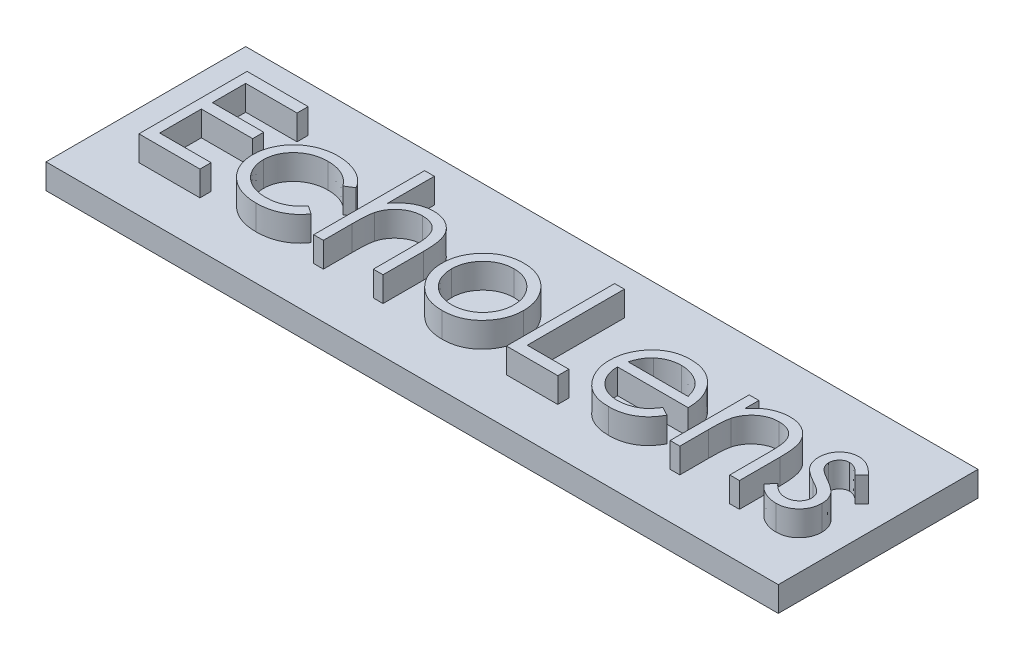
SolidWorks part; units mm, degrees
ref_plane "Front Plane" through (0, 0, 0) normal (0, 0, 1) x (1, 0, 0)
ref_plane "Top Plane" through (0, 0, 0) normal (0, 1, 0) x (1, 0, 0)
ref_plane "Right Plane" through (0, 0, 0) normal (1, 0, 0) x (0, 0, -1)
sketch "Sketch1" plane through (0, 0, 0) normal (0, 1, 0) x (1, 0, 0)
  line L0 (-20, 0) -> (20, 0) construction
  line L1 (-19.1667, 6.5) -> (-15.5, 6.5)
  line L2 (-15.5, 6.5) -> (-15.5, 5.8333)
  line L3 (-15.5, 5.8333) -> (-18.5833, 5.8333)
  line L4 (-18.5833, 5.8333) -> (-18.5833, 3.8333)
  line L5 (-18.5833, 3.8333) -> (-15.5, 3.8333)
  line L6 (-15.5, 3.8333) -> (-15.5, 3.1667)
  line L7 (-15.5, 3.1667) -> (-18.5833, 3.1667)
  line L8 (-18.5833, 3.1667) -> (-18.5833, 0.6667)
  line L9 (-18.5833, 0.6667) -> (-15.5, 0.6667)
  line L10 (-15.5, 0.6667) -> (-15.5, 0)
  line L11 (-15.5, 0) -> (-19.1667, 0)
  line L12 (-19.1667, 0) -> (-19.1667, 6.5)
  line L13 (-9.8333, 3.7201) -> (-10.3216, 3.4167)
  line L14 (-10.3216, 1.3333) -> (-9.8333, 1.013)
  line L15 (-8.6667, 6.6667) -> (-8.0833, 6.6667)
  line L16 (-8.0833, 6.6667) -> (-8.0833, 3.8529)
  line L17 (-4.5, 2.4258) -> (-4.5, 0)
  line L18 (-4.5, 0) -> (-5.0833, 0)
  line L19 (-5.0833, 0) -> (-5.0833, 2.2344)
  line L20 (-8.0833, 1.7174) -> (-8.0833, 0)
  line L21 (-8.0833, 0) -> (-8.6667, 0)
  line L22 (-8.6667, 0) -> (-8.6667, 6.6667)
  line L23 (2.9167, 6.5) -> (3.5, 6.5)
  line L24 (3.5, 6.5) -> (3.5, 0.6667)
  line L25 (3.5, 0.6667) -> (6, 0.6667)
  line L26 (6, 0.6667) -> (6, 0)
  line L27 (6, 0) -> (2.9167, 0)
  line L28 (2.9167, 0) -> (2.9167, 6.5)
  line L29 (10.8151, 1.5) -> (11.3333, 1.2279)
  line L30 (11.5833, 2.25) -> (7.3333, 2.25)
  line L31 (7.3945, 2.8333) -> (11, 2.8333)
  line L32 (12.75, 4.75) -> (13.3333, 4.75)
  line L33 (13.3333, 4.75) -> (13.3333, 3.8932)
  line L34 (16.9167, 2.4258) -> (16.9167, 0)
  line L35 (16.9167, 0) -> (16.3333, 0)
  line L36 (16.3333, 0) -> (16.3333, 2.2344)
  line L37 (13.3333, 1.7174) -> (13.3333, 0)
  line L38 (13.3333, 0) -> (12.75, 0)
  line L39 (12.75, 0) -> (12.75, 4.75)
  line L40 (20.5, 4.1576) -> (20.1042, 3.75)
  line L41 (17.8333, 0.5599) -> (18.2201, 1)
  line L43 (-22, 9.25) -> (22, 9.25)
  line L44 (-22, 9.25) -> (-22, -2.75)
  line L45 (-22, -2.75) -> (22, -2.75)
  line L46 (22, 9.25) -> (22, -2.75)
  spline S0 degree 3 poles (-10.3216, 3.4167) (-10.4224, 3.5511) (-10.5946, 3.7325) (-10.8586, 3.9283) (-11.0689, 4.0467) (-11.2944, 4.138) (-11.6201, 4.2264) (-11.877, 4.2503) (-12.0508, 4.25) knots 0 0 0 0 0.252584 0.373506 0.493364 0.614609 0.73847 1 1 1 1
  spline S1 degree 3 poles (-12.0508, 4.25) (-12.1908, 4.248) (-12.3987, 4.2357) (-12.6645, 4.1761) (-12.8521, 4.1183) (-13.0299, 4.0407) (-13.1982, 3.9464) (-13.3587, 3.8367) (-13.5065, 3.7096) (-13.6418, 3.5715) (-13.759, 3.4234) (-13.861, 3.2697) (-13.9411, 3.1068) (-14.0065, 2.9382) (-14.065, 2.699) (-14.084, 2.5135) (-14.0833, 2.388) knots 0 0 0 0 0.136921 0.201969 0.265462 0.328248 0.390817 0.45355 0.517542 0.580738 0.641922 0.701597 0.760313 0.818757 0.877718 1 1 1 1
  spline S2 degree 3 poles (-14.0833, 2.388) (-14.0829, 2.223) (-14.0506, 1.9744) (-13.9377, 1.6602) (-13.8226, 1.4342) (-13.6768, 1.2251) (-13.5056, 1.0376) (-13.3089, 0.8753) (-13.0884, 0.7406) (-12.8493, 0.6325) (-12.504, 0.5277) (-12.2309, 0.5007) (-12.0469, 0.5) knots 0 0 0 0 0.159965 0.240321 0.322529 0.405024 0.486597 0.567865 0.651333 0.736238 0.821529 1 1 1 1
  spline S3 degree 3 poles (-12.0469, 0.5) (-11.8779, 0.5001) (-11.6274, 0.5237) (-11.3088, 0.6127) (-11.0852, 0.7038) (-10.874, 0.8219) (-10.6058, 1.0188) (-10.4279, 1.1994) (-10.3216, 1.3333) knots 0 0 0 0 0.255447 0.377298 0.498442 0.619372 0.741857 1 1 1 1
  spline S4 degree 3 poles (-9.8333, 1.013) (-9.8897, 0.9272) (-9.9815, 0.8035) (-10.121, 0.6539) (-10.2323, 0.5497) (-10.3495, 0.4508) (-10.4764, 0.3619) (-10.6089, 0.2781) (-10.7487, 0.2027) (-10.8942, 0.1349) (-11.0453, 0.0766) (-11.2012, 0.0265) (-11.3623, -0.0133) (-11.5287, -0.0451) (-11.76, -0.0738) (-11.9367, -0.0852) (-12.056, -0.0833) knots 0 0 0 0 0.119069 0.178197 0.236957 0.295932 0.355856 0.416473 0.477742 0.539903 0.602538 0.665422 0.729765 0.794829 0.861827 1 1 1 1
  spline S5 degree 3 poles (-12.056, -0.0833) (-12.2366, -0.0852) (-12.5029, -0.0624) (-12.8456, 0.0111) (-13.0864, 0.0882) (-13.3154, 0.1876) (-13.5325, 0.3089) (-13.7368, 0.4533) (-13.9265, 0.6182) (-14.1006, 0.7969) (-14.2502, 0.9898) (-14.3799, 1.1897) (-14.4841, 1.4011) (-14.5669, 1.6211) (-14.6438, 1.9318) (-14.6672, 2.173) (-14.6667, 2.3359) knots 0 0 0 0 0.136335 0.201096 0.26445 0.327005 0.389391 0.451976 0.51567 0.578973 0.640167 0.69974 0.758685 0.81782 0.876984 1 1 1 1
  spline S6 degree 3 poles (-14.6667, 2.3359) (-14.6683, 2.4476) (-14.654, 2.6135) (-14.6213, 2.8322) (-14.5805, 2.9912) (-14.5332, 3.1483) (-14.4729, 3.3017) (-14.4022, 3.452) (-14.3219, 3.5989) (-14.2314, 3.7399) (-14.1314, 3.8732) (-14.0254, 4.0003) (-13.9087, 4.1167) (-13.786, 4.2273) (-13.654, 4.329) (-13.5134, 4.4221) (-13.3664, 4.5084) (-13.2129, 4.5852) (-13.054, 4.6514) (-12.8906, 4.7079) (-12.7224, 4.7527) (-12.5506, 4.7902) (-12.3122, 4.8223) (-12.1306, 4.834) (-12.0078, 4.8333) knots 0 0 0 0 0.082136 0.122636 0.162831 0.203007 0.243526 0.284173 0.32541 0.366855 0.407551 0.448187 0.488683 0.529015 0.569843 0.61137 0.653238 0.695446 0.737751 0.780043 0.822807 0.865978 0.909595 1 1 1 1
  spline S7 degree 3 poles (-12.0078, 4.8333) (-11.8526, 4.8338) (-11.6211, 4.8144) (-11.3179, 4.7561) (-11.0985, 4.6919) (-10.8891, 4.6142) (-10.6931, 4.5269) (-10.5151, 4.4255) (-10.3518, 4.3146) (-10.203, 4.1894) (-10.019, 3.9996) (-9.9014, 3.8368) (-9.8333, 3.7201) knots 0 0 0 0 0.182081 0.27191 0.362049 0.450066 0.533976 0.613602 0.690198 0.765413 0.841437 1 1 1 1
  spline S8 degree 3 poles (-8.0833, 3.8529) (-7.966, 4.0089) (-7.7716, 4.2191) (-7.4828, 4.4546) (-7.2593, 4.5919) (-7.0271, 4.7002) (-6.7025, 4.8039) (-6.4468, 4.833) (-6.276, 4.8333) knots 0 0 0 0 0.273996 0.400684 0.522555 0.641534 0.759969 1 1 1 1
  spline S9 degree 3 poles (-6.276, 4.8333) (-6.1045, 4.8322) (-5.8484, 4.8043) (-5.5317, 4.6878) (-5.315, 4.5706) (-5.1203, 4.4244) (-4.9479, 4.2558) (-4.8071, 4.0602) (-4.7112, 3.8796) (-4.6489, 3.7189) (-4.6094, 3.581) (-4.576, 3.4274) (-4.5468, 3.2581) (-4.5274, 3.0723) (-4.5056, 2.7934) (-4.4986, 2.5761) (-4.5, 2.4258) knots 0 0 0 0 0.151155 0.223454 0.295497 0.36692 0.436794 0.506696 0.577864 0.615912 0.658048 0.703776 0.75408 0.808979 0.867913 1 1 1 1
  spline S10 degree 3 poles (-5.0833, 2.2344) (-5.0842, 2.3581) (-5.0846, 2.5352) (-5.0916, 2.7605) (-5.0996, 2.9041) (-5.1082, 3.031) (-5.1224, 3.1665) (-5.1379, 3.2593) (-5.151, 3.3151) knots 0 0 0 0 0.342141 0.489871 0.623312 0.740056 0.841468 1 1 1 1
  spline S11 degree 3 poles (-5.151, 3.3151) (-5.1871, 3.4575) (-5.2624, 3.6607) (-5.4263, 3.8872) (-5.5708, 4.0208) (-5.739, 4.1255) (-6.0064, 4.2265) (-6.2273, 4.2507) (-6.3789, 4.25) knots 0 0 0 0 0.261954 0.379638 0.494379 0.609866 0.729887 1 1 1 1
  spline S12 degree 3 poles (-6.3789, 4.25) (-6.4717, 4.2504) (-6.6105, 4.2399) (-6.79, 4.2011) (-6.9207, 4.1623) (-7.0459, 4.1095) (-7.1691, 4.0483) (-7.2868, 3.9735) (-7.4012, 3.8895) (-7.5076, 3.7965) (-7.6066, 3.6983) (-7.6949, 3.5938) (-7.7749, 3.4846) (-7.8439, 3.3692) (-7.9247, 3.2082) (-7.9701, 3.08) (-7.9935, 2.9922) knots 0 0 0 0 0.126694 0.189084 0.250363 0.312516 0.374243 0.43785 0.502657 0.567745 0.630576 0.692772 0.754268 0.815121 0.876051 1 1 1 1
  spline S13 degree 3 poles (-7.9935, 2.9922) (-8.0109, 2.9236) (-8.0304, 2.8103) (-8.0495, 2.6461) (-8.0626, 2.4958) (-8.0707, 2.3269) (-8.0827, 2.0657) (-8.0825, 1.8602) (-8.0833, 1.7174) knots 0 0 0 0 0.165611 0.269045 0.387448 0.518827 0.665394 1 1 1 1
  spline S14 degree 3 poles (-0.8724, 4.8333) (-0.6977, 4.8351) (-0.4391, 4.8099) (-0.1083, 4.727) (0.1253, 4.6431) (0.3452, 4.5303) (0.6281, 4.3491) (0.8169, 4.1769) (0.9323, 4.0508) knots 0 0 0 0 0.258332 0.382134 0.503804 0.624693 0.746871 1 1 1 1
  spline S15 degree 3 poles (0.9323, 4.0508) (1.0382, 3.935) (1.1801, 3.7494) (1.3328, 3.4813) (1.424, 3.2729) (1.4958, 3.0568) (1.5648, 2.7542) (1.5825, 2.5197) (1.5833, 2.362) knots 0 0 0 0 0.253834 0.376506 0.498534 0.621368 0.744565 1 1 1 1
  spline S16 degree 3 poles (1.5833, 2.362) (1.5843, 2.2031) (1.5625, 1.967) (1.4908, 1.6617) (1.415, 1.4428) (1.3178, 1.2313) (1.1991, 1.0281) (1.0582, 0.8328) (0.8985, 0.6471) (0.722, 0.476) (0.5305, 0.3268) (0.3278, 0.199) (0.1111, 0.096) (-0.1174, 0.0149) (-0.4444, -0.0628) (-0.6998, -0.0827) (-0.8724, -0.0833) knots 0 0 0 0 0.123337 0.183265 0.243172 0.302898 0.363774 0.425605 0.489659 0.553785 0.616222 0.677854 0.739517 0.802097 0.865866 1 1 1 1
  spline S17 degree 3 poles (-0.8724, -0.0833) (-1.0459, -0.0825) (-1.3022, -0.0631) (-1.63, 0.0149) (-1.8589, 0.0963) (-2.0764, 0.199) (-2.2803, 0.3264) (-2.472, 0.476) (-2.6485, 0.6471) (-2.8082, 0.8328) (-2.9491, 1.0281) (-3.0678, 1.2313) (-3.165, 1.4428) (-3.2408, 1.6617) (-3.3125, 1.967) (-3.3343, 2.2031) (-3.3333, 2.362) knots 0 0 0 0 0.134635 0.198324 0.260825 0.322714 0.384555 0.446913 0.510958 0.574931 0.636685 0.697483 0.757134 0.816966 0.876818 1 1 1 1
  spline S18 degree 3 poles (-3.3333, 2.362) (-3.3324, 2.5193) (-3.3147, 2.7533) (-3.2459, 3.0551) (-3.1741, 3.2704) (-3.0821, 3.4779) (-2.9314, 3.7467) (-2.7871, 3.9308) (-2.6823, 4.0469) knots 0 0 0 0 0.255238 0.378679 0.501088 0.622714 0.746241 1 1 1 1
  spline S19 degree 3 poles (-2.6823, 4.0469) (-2.5679, 4.1747) (-2.3775, 4.3453) (-2.0952, 4.5301) (-1.8729, 4.6407) (-1.6395, 4.7275) (-1.3073, 4.8099) (-1.048, 4.8349) (-0.8724, 4.8333) knots 0 0 0 0 0.252713 0.374819 0.496436 0.617911 0.741288 1 1 1 1
  spline S20 degree 3 poles (-0.875, 4.25) (-0.9994, 4.2497) (-1.1843, 4.2329) (-1.4219, 4.1751) (-1.5917, 4.1146) (-1.7545, 4.0364) (-1.9103, 3.9404) (-2.0597, 3.8278) (-2.1997, 3.6988) (-2.3282, 3.5579) (-2.4405, 3.4077) (-2.536, 3.2508) (-2.6156, 3.0869) (-2.6748, 2.9144) (-2.7331, 2.6726) (-2.7497, 2.4846) (-2.75, 2.3581) knots 0 0 0 0 0.126044 0.187165 0.247399 0.30838 0.36978 0.432584 0.497641 0.562401 0.625557 0.687332 0.748313 0.809791 0.871768 1 1 1 1
  spline S21 degree 3 poles (-2.75, 2.3581) (-2.7496, 2.1934) (-2.7206, 1.9458) (-2.6123, 1.6338) (-2.5036, 1.4117) (-2.3672, 1.2062) (-2.2066, 1.0229) (-2.0234, 0.8647) (-1.8198, 0.7334) (-1.6, 0.6293) (-1.2873, 0.5292) (-1.0409, 0.4981) (-0.875, 0.5) knots 0 0 0 0 0.168179 0.251488 0.335841 0.419834 0.502345 0.583649 0.665931 0.748717 0.831047 1 1 1 1
  spline S22 degree 3 poles (-0.875, 0.5) (-0.7092, 0.4983) (-0.463, 0.5287) (-0.1509, 0.6296) (0.0686, 0.7333) (0.2721, 0.8652) (0.4566, 1.022) (0.6159, 1.2067) (0.7521, 1.412) (0.8625, 1.6335) (0.9704, 1.9459) (0.9997, 2.1933) (1, 2.3581) knots 0 0 0 0 0.168983 0.250908 0.333708 0.416005 0.49766 0.579893 0.663902 0.748466 0.831791 1 1 1 1
  spline S23 degree 3 poles (1, 2.3581) (0.9997, 2.4846) (0.9831, 2.6726) (0.9248, 2.9144) (0.8655, 3.0868) (0.7862, 3.2512) (0.6889, 3.4073) (0.577, 3.5584) (0.447, 3.6983) (0.3072, 3.8278) (0.1577, 3.9404) (0.0021, 4.036) (-0.1602, 4.1153) (-0.33, 4.1746) (-0.5669, 4.2333) (-0.7511, 4.2493) (-0.875, 4.25) knots 0 0 0 0 0.128274 0.19027 0.251768 0.312769 0.374793 0.43797 0.503047 0.568125 0.63095 0.692369 0.752973 0.813641 0.874355 1 1 1 1
  spline S24 degree 3 poles (11.3333, 1.2279) (11.2563, 1.0836) (11.1272, 0.8812) (10.9286, 0.6402) (10.7706, 0.4884) (10.6041, 0.356) (10.4282, 0.2403) (10.2419, 0.1416) (10.0453, 0.0585) (9.8368, -0.0053) (9.5352, -0.0672) (9.2996, -0.0833) (9.1393, -0.0833) knots 0 0 0 0 0.181661 0.265874 0.346355 0.4246 0.501903 0.579992 0.658443 0.738672 0.821894 1 1 1 1
  spline S25 degree 3 poles (9.1393, -0.0833) (8.9615, -0.0833) (8.6998, -0.0628) (8.3669, 0.0173) (8.1381, 0.0989) (7.925, 0.2055) (7.7272, 0.3355) (7.5437, 0.488) (7.3802, 0.6644) (7.233, 0.8533) (7.1032, 1.0501) (6.9946, 1.2543) (6.9063, 1.4646) (6.835, 1.6798) (6.768, 1.9778) (6.7517, 2.2078) (6.75, 2.362) knots 0 0 0 0 0.139629 0.204797 0.268135 0.329814 0.391301 0.453434 0.516552 0.579631 0.641119 0.701294 0.76081 0.819932 0.87892 1 1 1 1
  spline S26 degree 3 poles (6.75, 2.362) (6.7518, 2.5065) (6.7653, 2.7221) (6.824, 3.0017) (6.8837, 3.2039) (6.9609, 3.3999) (7.0875, 3.6553) (7.2086, 3.8337) (7.2969, 3.9479) knots 0 0 0 0 0.253768 0.377428 0.500551 0.623296 0.746578 1 1 1 1
  spline S27 degree 3 poles (7.2969, 3.9479) (7.4094, 4.0885) (7.5928, 4.2852) (7.88, 4.4909) (8.1058, 4.6172) (8.3479, 4.7131) (8.6943, 4.8106) (8.9689, 4.8311) (9.1536, 4.8333) knots 0 0 0 0 0.253589 0.374643 0.49534 0.616325 0.739759 1 1 1 1
  spline S28 degree 3 poles (9.1536, 4.8333) (9.3446, 4.8341) (9.6267, 4.8065) (9.9844, 4.7075) (10.233, 4.6052) (10.4664, 4.473) (10.7603, 4.2519) (10.9524, 4.0482) (11.0664, 3.8984) knots 0 0 0 0 0.259033 0.38188 0.502258 0.622752 0.744743 1 1 1 1
  spline S29 degree 3 poles (11.0664, 3.8984) (11.1516, 3.7891) (11.2629, 3.6115) (11.381, 3.3574) (11.4523, 3.1552) (11.5099, 2.9438) (11.5667, 2.6423) (11.5804, 2.4083) (11.5833, 2.25) knots 0 0 0 0 0.236255 0.356174 0.47725 0.60154 0.729618 1 1 1 1
  spline S30 degree 3 poles (7.3333, 2.25) (7.3367, 2.127) (7.3531, 1.9452) (7.4094, 1.7127) (7.4674, 1.551) (7.5377, 1.397) (7.6239, 1.2518) (7.7267, 1.1162) (7.8413, 0.9888) (7.9689, 0.8754) (8.1031, 0.7739) (8.2459, 0.6889) (8.3962, 0.6198) (8.5536, 0.5658) (8.7764, 0.5155) (8.9494, 0.4994) (9.0664, 0.5) knots 0 0 0 0 0.134476 0.198391 0.260753 0.321829 0.383037 0.444653 0.507398 0.569825 0.630778 0.690929 0.750945 0.811049 0.872331 1 1 1 1
  spline S31 degree 3 poles (9.0664, 0.5) (9.1819, 0.4994) (9.3552, 0.513) (9.5815, 0.5604) (9.7472, 0.6085) (9.9062, 0.6671) (10.0533, 0.7379) (10.1887, 0.8162) (10.3152, 0.9057) (10.4378, 1.0153) (10.6115, 1.21) (10.7361, 1.3764) (10.8151, 1.5) knots 0 0 0 0 0.163879 0.245659 0.327726 0.40861 0.485749 0.559169 0.630268 0.705306 0.792065 1 1 1 1
  spline S32 degree 3 poles (11, 2.8333) (10.9631, 2.9833) (10.8895, 3.1948) (10.7549, 3.4491) (10.6406, 3.6081) (10.5109, 3.7492) (10.3611, 3.8726) (10.1932, 3.9829) (10.0079, 4.0761) (9.8117, 4.1552) (9.5372, 4.2269) (9.3256, 4.2521) (9.1836, 4.25) knots 0 0 0 0 0.185231 0.267501 0.3444 0.419595 0.496891 0.576638 0.660268 0.745387 0.83004 1 1 1 1
  spline S33 degree 3 poles (9.1836, 4.25) (9.0686, 4.2503) (8.8977, 4.2378) (8.6779, 4.1901) (8.5206, 4.1419) (8.3709, 4.0776) (8.1758, 3.9765) (8.0442, 3.8758) (7.9596, 3.8047) knots 0 0 0 0 0.259141 0.384162 0.505992 0.629098 0.750669 1 1 1 1
  spline S34 degree 3 poles (7.9596, 3.8047) (7.8949, 3.7501) (7.8072, 3.6556) (7.7018, 3.5167) (7.6287, 3.3997) (7.5618, 3.2723) (7.4759, 3.0854) (7.4251, 2.9361) (7.3945, 2.8333) knots 0 0 0 0 0.22258 0.3385 0.458709 0.585535 0.717518 1 1 1 1
  spline S35 degree 3 poles (13.3333, 3.8932) (13.451, 4.0459) (13.6384, 4.2593) (13.9305, 4.4832) (14.1533, 4.6135) (14.3867, 4.7115) (14.7126, 4.8073) (14.9689, 4.8324) (15.1406, 4.8333) knots 0 0 0 0 0.273569 0.398988 0.51993 0.63811 0.756589 1 1 1 1
  spline S36 degree 3 poles (15.1406, 4.8333) (15.3122, 4.8322) (15.5682, 4.8043) (15.885, 4.6878) (16.1016, 4.5705) (16.2968, 4.4245) (16.4683, 4.2544) (16.6101, 4.0588) (16.7052, 3.8773) (16.7678, 3.7163) (16.8072, 3.5784) (16.8407, 3.4248) (16.8698, 3.2559) (16.8894, 3.0706) (16.911, 2.7925) (16.9181, 2.5756) (16.9167, 2.4258) knots 0 0 0 0 0.151178 0.223488 0.295543 0.366976 0.437131 0.507044 0.57856 0.616614 0.658756 0.704491 0.754803 0.809332 0.868274 1 1 1 1
  spline S37 degree 3 poles (16.3333, 2.2344) (16.3324, 2.3581) (16.3322, 2.5352) (16.3249, 2.7605) (16.3176, 2.9042) (16.3068, 3.0309) (16.2932, 3.1665) (16.2774, 3.2593) (16.2643, 3.3151) knots 0 0 0 0 0.34211 0.489826 0.623254 0.74008 0.841483 1 1 1 1
  spline S38 degree 3 poles (16.2643, 3.3151) (16.2318, 3.4577) (16.1581, 3.6613) (15.9942, 3.8871) (15.8496, 4.0212) (15.6802, 4.1254) (15.4119, 4.2261) (15.1907, 4.2509) (15.0391, 4.25) knots 0 0 0 0 0.260833 0.378476 0.493178 0.609281 0.729981 1 1 1 1
  spline S39 degree 3 poles (15.0391, 4.25) (14.9463, 4.2504) (14.8075, 4.2399) (14.628, 4.2011) (14.4972, 4.1624) (14.3718, 4.1091) (14.2478, 4.0487) (14.1299, 3.9734) (14.0155, 3.8895) (13.9091, 3.7965) (13.81, 3.6983) (13.7217, 3.5938) (13.6417, 3.4846) (13.5727, 3.3692) (13.4919, 3.2082) (13.4466, 3.08) (13.4232, 2.9922) knots 0 0 0 0 0.126627 0.188984 0.25023 0.312351 0.374574 0.438148 0.50292 0.567974 0.630771 0.692935 0.754398 0.815218 0.876117 1 1 1 1
  spline S40 degree 3 poles (13.4232, 2.9922) (13.4058, 2.9227) (13.3864, 2.8086) (13.3672, 2.6435) (13.354, 2.4932) (13.3461, 2.3247) (13.3339, 2.0644) (13.3342, 1.8598) (13.3333, 1.7174) knots 0 0 0 0 0.167615 0.271052 0.38946 0.520843 0.666399 1 1 1 1
  spline S41 degree 3 poles (20.1042, 3.75) (20.0395, 3.8271) (19.9402, 3.9347) (19.7957, 4.0536) (19.6935, 4.126) (19.5905, 4.1806) (19.4566, 4.233) (19.3522, 4.2499) (19.2839, 4.25) knots 0 0 0 0 0.305036 0.441309 0.565963 0.683525 0.793334 1 1 1 1
  spline S42 degree 3 poles (19.2839, 4.25) (19.2028, 4.2517) (19.0819, 4.2255) (18.9383, 4.1446) (18.8451, 4.0593) (18.7663, 3.9613) (18.6889, 3.8149) (18.6669, 3.6923) (18.6667, 3.6107) knots 0 0 0 0 0.245901 0.369166 0.498511 0.628504 0.751028 1 1 1 1
  spline S43 degree 3 poles (18.6667, 3.6107) (18.6668, 3.5357) (18.6959, 3.3794) (18.7786, 3.2438) (18.8281, 3.1797) knots 0 0 0 0 0.479403 1 1 1 1
  spline S44 degree 3 poles (18.8281, 3.1797) (18.8578, 3.1394) (18.9158, 3.0845) (19.0004, 3.0099) (19.0808, 2.9505) (19.1714, 2.8881) (19.3141, 2.8) (19.4259, 2.7321) (19.5065, 2.6901) knots 0 0 0 0 0.17756 0.283982 0.402217 0.533568 0.676121 1 1 1 1
  spline S45 degree 3 poles (19.5065, 2.6901) (19.6044, 2.636) (19.7453, 2.5545) (19.9193, 2.4378) (20.0334, 2.3549) (20.1336, 2.271) (20.2481, 2.1666) (20.3208, 2.0816) (20.362, 2.0234) knots 0 0 0 0 0.307115 0.446213 0.574876 0.694152 0.804581 1 1 1 1
  spline S46 degree 3 poles (20.362, 2.0234) (20.4327, 1.9166) (20.5517, 1.6814) (20.5815, 1.4195) (20.5833, 1.2891) knots 0 0 0 0 0.495235 1 1 1 1
  spline S47 degree 3 poles (20.5833, 1.2891) (20.5825, 1.1967) (20.5722, 1.0591) (20.5295, 0.8832) (20.4867, 0.7575) (20.4288, 0.6387) (20.3609, 0.5239) (20.2794, 0.4155) (20.1864, 0.3136) (20.0845, 0.2206) (19.9759, 0.1388) (19.8603, 0.0709) (19.7386, 0.0147) (19.6105, -0.03) (19.4285, -0.072) (19.2868, -0.0827) (19.1914, -0.0833) knots 0 0 0 0 0.127199 0.188597 0.24864 0.309525 0.370037 0.431889 0.495704 0.559519 0.621372 0.682397 0.743568 0.805498 0.86864 1 1 1 1
  spline S48 degree 3 poles (19.1914, -0.0833) (19.0609, -0.0843) (18.8656, -0.0618) (18.6138, 0.0101) (18.4311, 0.0837) (18.2583, 0.177) (18.048, 0.3248) (17.9118, 0.4604) (17.8333, 0.5599) knots 0 0 0 0 0.251724 0.377219 0.504694 0.631458 0.755401 1 1 1 1
  spline S49 degree 3 poles (18.2201, 1) (18.29, 0.9222) (18.3982, 0.8132) (18.5577, 0.6953) (18.6743, 0.6235) (18.7936, 0.5683) (18.9542, 0.5164) (19.0789, 0.4996) (19.1615, 0.5) knots 0 0 0 0 0.285904 0.417172 0.540501 0.659238 0.775006 1 1 1 1
  spline S50 degree 3 poles (19.1615, 0.5) (19.2714, 0.499) (19.4345, 0.5274) (19.6308, 0.6236) (19.7572, 0.7239) (19.8646, 0.8409) (19.9688, 1.016) (20.0006, 1.1655) (20, 1.2643) knots 0 0 0 0 0.261896 0.387836 0.517686 0.644509 0.764718 1 1 1 1
  spline S51 degree 3 poles (20, 1.2643) (19.9997, 1.346) (19.9737, 1.5099) (19.8916, 1.6544) (19.8398, 1.7174) knots 0 0 0 0 0.500453 1 1 1 1
  spline S52 degree 3 poles (19.8398, 1.7174) (19.8086, 1.7551) (19.7506, 1.8097) (19.6616, 1.8804) (19.5779, 1.9405) (19.4813, 2.0029) (19.3278, 2.0932) (19.2059, 2.1616) (19.1198, 2.207) knots 0 0 0 0 0.167462 0.27227 0.389551 0.520801 0.666263 1 1 1 1
  spline S53 degree 3 poles (19.1198, 2.207) (19.0258, 2.259) (18.8903, 2.3364) (18.7249, 2.4509) (18.6151, 2.5306) (18.5183, 2.6113) (18.4107, 2.716) (18.3397, 2.7978) (18.3008, 2.8555) knots 0 0 0 0 0.30595 0.443775 0.572824 0.692154 0.802296 1 1 1 1
  spline S54 degree 3 poles (18.3008, 2.8555) (18.2279, 2.9602) (18.1194, 3.1977) (18.081, 3.4559) (18.0833, 3.5872) knots 0 0 0 0 0.492591 1 1 1 1
  spline S55 degree 3 poles (18.0833, 3.5872) (18.0839, 3.6729) (18.0916, 3.8004) (18.13, 3.963) (18.1654, 4.0784) (18.2145, 4.1871) (18.2733, 4.2904) (18.3424, 4.3884) (18.4219, 4.4794) (18.5094, 4.562) (18.6039, 4.6341) (18.7034, 4.6956) (18.8081, 4.7471) (18.9192, 4.7861) (19.0774, 4.8228) (19.2004, 4.8343) (19.2839, 4.8333) knots 0 0 0 0 0.133044 0.196507 0.258613 0.319728 0.380873 0.442636 0.505079 0.567881 0.628814 0.68891 0.748765 0.809386 0.870884 1 1 1 1
  spline S56 degree 3 poles (19.2839, 4.8333) (19.3858, 4.8332) (19.5416, 4.8115) (19.742, 4.7401) (19.8949, 4.6655) (20.0468, 4.5687) (20.2575, 4.4074) (20.406, 4.264) (20.5, 4.1576) knots 0 0 0 0 0.213412 0.326127 0.444452 0.569061 0.702712 1 1 1 1
  point P3 (0, 0)
  point P4 (0, 0)
  point P654 (0, 0)
  point P655 (0, 0)
  point P656 (0, -2.75)
  dimension "D1" = 40
  dimension "D2" = 44
  dimension "D3" = 12
  dimension "D4" = 2.75
extrude "Boss-Extrude1" add sketch "Sketch1" against normal blind 1.5 contours L46 L43 L44 L45 L11 L12 L1 L2 L3 L4 L5 L6 L7 L8 L9 L10 S5 S6 S7 L13 S0 S1 S2 S3 L14 S4 L22 L15 L16 S8 S9 L17 S17 S18 S19 S14 S15 S16 L28 L23 L24 L25 L26 | S48 L0 S47 S46 S45 S44 S43 S42 S41 L40 S56 S55 S54 S53 S52 S51 S50 S49 L41 | S25 L0 S24 L29 S31 S30 L30 S29 S28 S27 S26 S34 S33 S32 L31 | S33 S34 L31 S32 | S17 L0 S16 S15 S14 S19 S18 S23 S22 S21 S20 | S22 S23 S20 S21 | L28 L27 L26 L25 L24 L23 | S40 S39 S38 S37 L36 L35 L34 S36 S35 L33 L32 L39 L38 L37 | L37 L0 L36 S37 S38 S39 S40 | S13 S12 S11 S10 L19 L18 L17 S9 S8 L16 L15 L22 L21 L20 | L20 L0 L19 S10 S11 S12 S13 | S5 L0 S4 L14 S3 S2 S1 S0 L13 S7 S6 | L12 L11 L10 L9 L8 L7 L6 L5 L4 L3 L2 L1 | L0 S5 S4 | L0 S17 S16 | L0 S25 S24 | L0 S48 S47 region at (-17.7397, 0, -3.3016) region at (19.2851, 0, -2.3436) region at (19.181, 0, 0.0336) region at (12.8138, 0, -2.375) region at (9.0407, 0, -2.4483) region at (9.1433, 0, 0.0337) region at (2.9886, 0, -3.25) region at (-2.7873, 0, -0.9242) region at (-0.8736, 0, 0.0335) region at (-8.588, 0, -3.3333) region at (-14.0812, 0, -0.8869) region at (-12.0501, 0, 0.0338) region at (-6.5549, 0, -1.9746) region at (14.862, 0, -1.9749) region at (9.2005, 0, -3.4293) region at (0, 0, -8.7939) region at (-0.8753, 0, -2.3686)
extrude "Boss-Extrude2" add sketch "Sketch1<3>" along normal blind 1.5 contours S48 L0 S47 S46 S45 S44 S43 S42 S41 L40 S56 S55 S54 S53 S52 S51 S50 S49 L41 | L0 S48 S47 | S40 S39 S38 S37 L36 L35 L34 S36 S35 L33 L32 L39 L38 L37 | S25 L0 S24 L29 S31 S30 L30 S29 S28 S27 S26 S34 S33 S32 L31 | L0 S25 S24 | L28 L27 L26 L25 L24 L23 | S17 L0 S16 S15 S14 S19 S18 S23 S22 S21 S20 | L0 S17 S16 | S13 S12 S11 S10 L19 L18 L17 S9 S8 L16 L15 L22 L21 L20 | S5 L0 S4 L14 S3 S2 S1 S0 L13 S7 S6 | L12 L11 L10 L9 L8 L7 L6 L5 L4 L3 L2 L1 | L0 S5 S4 region at (-17.7397, 0, -3.3016) region at (19.2851, 0, -2.3436) region at (19.181, 0, 0.0336) region at (12.8138, 0, -2.375) region at (9.0407, 0, -2.4483) region at (9.1433, 0, 0.0337) region at (2.9886, 0, -3.25) region at (-2.7873, 0, -0.9242) region at (-0.8736, 0, 0.0335) region at (-8.588, 0, -3.3333) region at (-14.0812, 0, -0.8869) region at (-12.0501, 0, 0.0338)
sketch "Sketch1<3>" plane through (0, 0, 0) normal (0, 1, 0) x (1, 0, 0) same geometry as "Sketch1"
